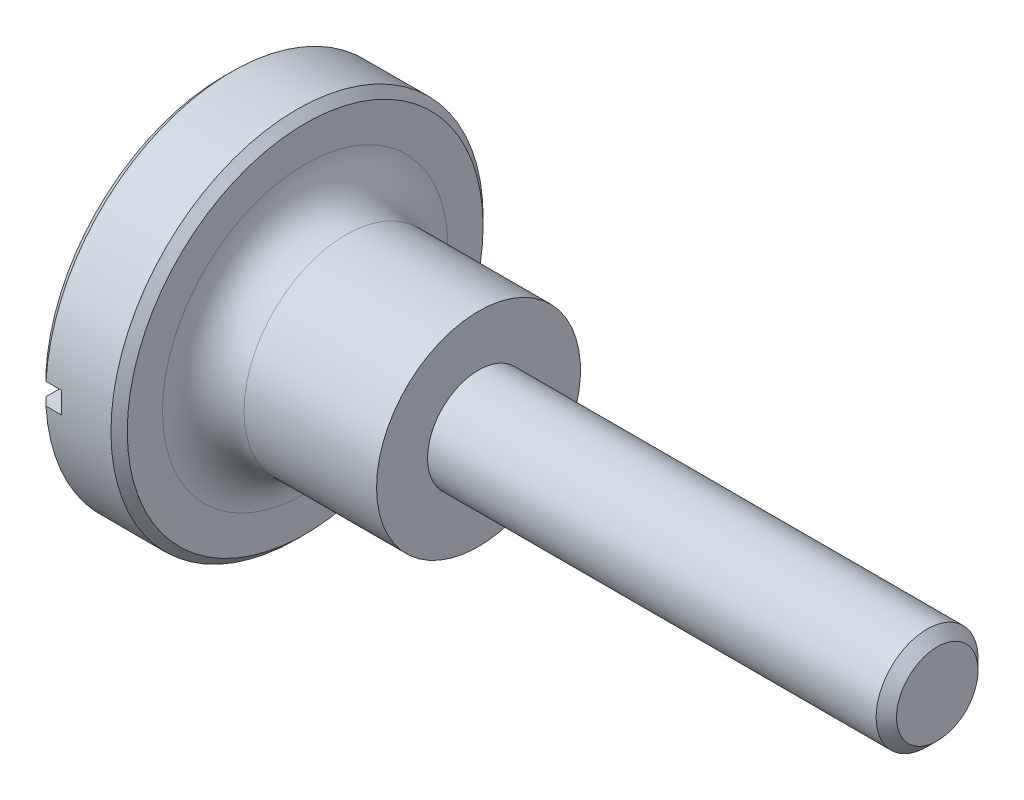
SolidWorks part; units mm, degrees
revolve "Base-Revolve" add sketch "BodySke" angle 360 about L2 other way angle 60
sketch "BodySke" plane through (0, 0, 0) normal (0, 0, 1) x (1, 0, 0)
  line L0 (69, 5) -> (70, 4)
  line L1 (0, 0) -> (0, 17.45)
  line L2 (-25.4, 0) -> (127, 0) construction
  line L3 (70, 0) -> (0, 0)
  line L5 (70, 4) -> (70, 0)
  line L6 (0.8, 18.25) -> (7.2, 18.25)
  line L7 (4, 31.75) -> (4, -6.35) construction
  line L8 (0.8, 18.25) -> (0, 17.45)
  line L9 (10, 6.5875) -> (10, -2.9375) construction
  line L10 (30, 6.35) -> (30, -3.175) construction
  line L11 (7.2, 18.25) -> (8, 17.45)
  line L12 (8, 10) -> (25, 10)
  line L13 (25, 10) -> (25, 5)
  line L14 (25, 5) -> (69, 5)
  line L15 (8, 10) -> (8, 17.45)
  point P9 (70, 5)
  dimension "D1" = 45
  dimension "Thread_nom" = 40
  dimension "Head_ht" = 8
  dimension "Head_dia" = 36.5
  dimension "Advance" = 2
  dimension "Length" = 45
  dimension "D3" = 45
cosmetic thread "ThreadCosmetic" [suppressed] parameters "Thread_length"=40, "Thread_minor"=8
ref_plane "Plane1" through (0, 0, 0) normal (0, 0, 1) x (1, 0, 0)
ref_plane "Plane2" through (0, 0, 0) normal (0, 1, 0) x (1, 0, 0)
ref_plane "Plane3" through (0, 0, 0) normal (1, 0, 0) x (0, 0, -1)
sketch "ThdSchSke" plane through (0, 0, 0) normal (0, 0, 1) x (1, 0, 0)
  line L0 (30, -4) -> (29.2998, -5)
  line L1 (30, -4) -> (30.7002, -5)
  line L2 (30.7002, -5) -> (30.7002, -6.25)
  line L3 (-3.175, 0) -> (5.1513, 0) construction
  line L5 (30.7002, -6.25) -> (29.2998, -6.25)
  line L6 (29.2998, -6.25) -> (29.2998, -5)
  line L7 (25, -10) -> (25, 10) construction
  dimension "Thread_minor" = 8
  dimension "Diameter" = 10
  dimension "Start" = 5
revolve "ThreadSchematic" [suppressed] cut sketch "ThdSchSke" angle 360 about L3
pattern_linear "ThdSchPat" [suppressed]
sketch "KnurlSke" plane through (0, 0, 0) normal (-1, 0, 0) x (0, 0, 1)
  line L0 (0, 17.65) -> (0, 3.175) construction
  line L1 (0, 17.65) -> (0.3445, 18.2467)
  line L2 (0, 17.65) -> (-0.3445, 18.2467)
  line L3 (0, 18.25) -> (0, 17.65) construction
  circle A0 centre (0, 0) radius 18.25 construction
  arc A1 (0.3445, 18.2467) -> (-0.3445, 18.2467) centre (0, 0) ccw
  dimension "D2" = 60
extrude "Knurl_cut" [suppressed] cut sketch "KnurlSke" against normal up to next
pattern_circular "Knurl" [suppressed] count 86 over 360 about axis through (-25.4, 0, 0) along (1, 0, 0)
sketch "SlotSke" plane through (0, 0, 0) normal (0, 0, 1) x (1, 0, 0)
  line L0 (2.3466, 1.0507) -> (-2.3466, -1.0507) construction
  line L1 (-2.3466, -1.0507) -> (2.3466, -1.0507)
  line L2 (-2.3466, -1.0507) -> (-2.3466, 1.0507)
  line L3 (-2.3466, 1.0507) -> (2.3466, 1.0507)
  line L4 (2.3466, -1.0507) -> (2.3466, 1.0507)
  dimension "Slot_dep" = 2.3466
  dimension "Slot_Wid" = 2.1014
extrude "Slot" cut sketch "SlotSke" against normal through all and the other way through all
fillet "Fillet1" radius 4 1 edges at (8, 0, 10)
equation "\"Thread_minor@ThreadCosmetic\" = \"Minor_dia@BodySke\""
equation "\"Thread_length@ThreadCosmetic\" = ((sgn( (\"Length@BodySke\" - \"Advance@BodySke\" * 2.0 ) - \"Thread_nom@BodySke\" )-1)*( (\"Length@BodySke\" - \"Advance@BodySke\" * 2.0 ) - \"Thread_nom@BodySke\" ))/-2+ \"Thread_nom@BodySke\""
equation "\"Thread_minor@ThdSchSke\" = \"Thread_minor@ThreadCosmetic\""
equation "\"Diameter@ThdSchSke\" = \"diameter@BodySke\""
equation "\"Overcut@ThdSchSke\" = \"diameter@BodySke\" * 1.25"
equation "\"Start@ThdSchSke\" =  \"Length@BodySke\" -  \"Thread_length@ThreadCosmetic\"  '---Non-countersunk---"
equation "\"Num_threads@ThdSchPat\" = int( \"Thread_length@ThreadCosmetic\" / \"Advance@BodySke\" + 0.999 )  + 1"
equation "\"Advance@ThdSchPat\" = \"Thread_length@ThreadCosmetic\" /  (\"Num_threads@ThdSchPat\" - 1) 'relax it"
equation "\"depth@KnurlSke\" = \"Chamfer@BodySke\" * 0.75"
equation "\"Count@Knurl\" = (3.141592654 / 2 * \"Head_dia@BodySke\") / \"depth@KnurlSke\" * 0.9"
